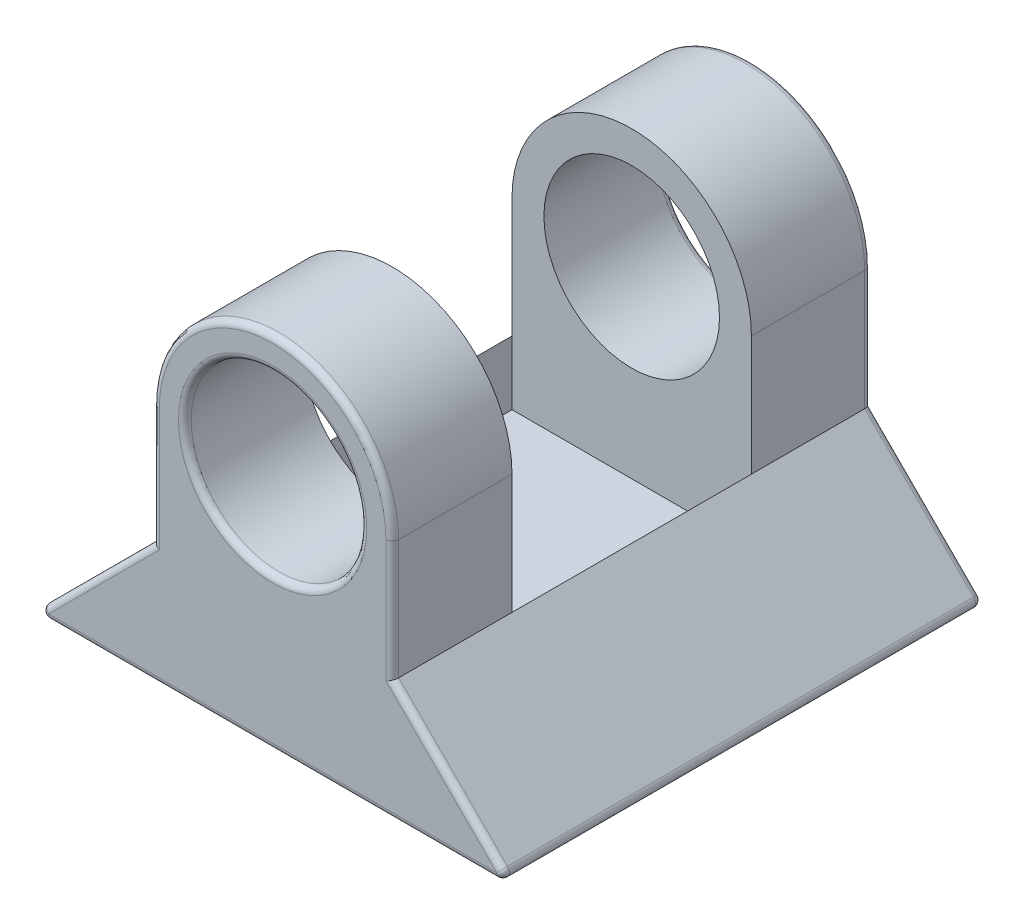
SolidWorks part; units mm, degrees
ref_plane "前视基准面" through (0, 0, 0) normal (0, 0, 1) x (1, 0, 0)
ref_plane "上视基准面" through (0, 0, 0) normal (0, 1, 0) x (1, 0, 0)
ref_plane "右视基准面" through (0, 0, 0) normal (1, 0, 0) x (0, 0, -1)
sketch "草图1" plane through (0, 0, 0) normal (0, 0, 1) x (1, 0, 0)
  line L0 (-7.5, 0) -> (7.5, 0)
  line L1 (-3.75, 3.75) -> (-7.5, 0)
  line L3 (-3.75, 7.5) -> (-3.75, 3.75)
  line L5 (3.75, 7.5) -> (3.75, 3.75)
  line L6 (3.75, 3.75) -> (7.5, 0)
  circle A0 centre (0, 7.5) radius 2.75
  arc A1 (3.75, 7.5) -> (-3.75, 7.5) centre (0, 7.5) ccw
extrude "凸台-拉伸1" add sketch "草图1" against normal blind 7.5 and the other way blind 7.5
sketch "草图2" plane through (0, 0, 0) normal (0, 0, 1) x (1, 0, 0)
  line L1 (-3.75, 3.75) -> (3.75, 3.75)
  line L2 (-3.75, 3.75) -> (-3.75, 12)
  line L3 (-3.75, 12) -> (3.75, 12)
  line L4 (3.75, 3.75) -> (3.75, 12)
extrude "切除-拉伸1" cut sketch "草图2" against normal blind 3.75 and the other way blind 3.75
sketch "草图3" plane through (0, 3.75, 0) normal (0, 1, 0) x (-1, 0, 0)
  line L1 (3.75, 3.75) -> (-3.75, 3.75)
  line L2 (3.75, 3.75) -> (3.75, -3.75)
  line L3 (3.75, -3.75) -> (-3.75, -3.75)
  line L4 (-3.75, 3.75) -> (-3.75, -3.75)
extrude "切除-拉伸2" cut sketch "草图3" against normal blind 2
sketch "草图4" plane through (0, 0, 0) normal (0, -1, 0) x (1, 0, 0)
  line L1 (-1.5, -1.5) -> (1.5, -1.5)
  line L2 (-1.5, -1.5) -> (-1.5, 1.5)
  line L3 (-1.5, 1.5) -> (1.5, 1.5)
  line L4 (1.5, -1.5) -> (1.5, 1.5)
extrude "凸台-拉伸2" add sketch "草图4" along normal blind 1
sketch "草图5" plane through (0, 0, 0) normal (0, 0, 1) x (1, 0, 0)
  line L0 (-1.95, -2.5) -> (1.95, -2.5)
  line L1 (-1.95, -2.5) -> (-1.95, -1.5556)
  line L2 (1.95, -2.5) -> (1.95, -1.5556)
  line L4 (-1.5, -1) -> (-1.5, 0) construction
  line L5 (-1.5, -0.6771) -> (1.5, -0.6771)
  arc A0 (-1.5, -0.6771) -> (-1.95, -1.5556) centre (0, -2) ccw
  arc A1 (1.95, -1.5556) -> (1.5, -0.6771) centre (0, -2) ccw
extrude "凸台-拉伸3" add sketch "草图5" along normal blind 2 and the other way blind 2
sketch "草图6" plane through (0, 0, 0) normal (1, 0, 0) x (0, 0, -1)
  line L0 (1.95, -2.5) -> (1.95, -1.5556)
  line L1 (2, -2.5) -> (1.95, -2.5)
  line L2 (2, -2.5) -> (2, -0.6771)
  line L3 (2, -0.6771) -> (1.5, -0.6771)
  line L4 (-2, -2.5) -> (-2, -0.6771)
  line L5 (-1.95, -2.5) -> (-1.95, -1.5556)
  line L6 (-1.5, -0.6771) -> (-2, -0.6771)
  line L7 (-1.95, -2.5) -> (-2, -2.5)
  arc A1 (-1.5, -0.6771) -> (-1.95, -1.5556) centre (0, -2) ccw
  arc A2 (1.95, -1.5556) -> (1.5, -0.6771) centre (0, -2) ccw
extrude "切除-拉伸3" cut sketch "草图6" against normal up to next and the other way up to next
fillet "圆角1" radius 0.1 4 edges at (0, -2.5, -1.95) (-1.95, -2.5, 0) (0, -2.5, 1.95) (1.95, -2.5, 0)
fillet "圆角2" radius 0.2 16 edges at (2.75, 7.5, 7.5) (0, 0, 7.5) (-5.625, 1.875, 7.5) (-3.75, 5.625, 7.5) (0, 11.25, 7.5) (3.75, 5.625, 7.5) (5.625, 1.875, 7.5) (3.75, 5.625, -7.5) (0, 11.25, -7.5) (-3.75, 5.625, -7.5) (-5.625, 1.875, -7.5) (0, 0, -7.5) (5.625, 1.875, -7.5) (2.75, 7.5, -7.5) (-7.5, 0, 0) (7.5, 0, 0)
